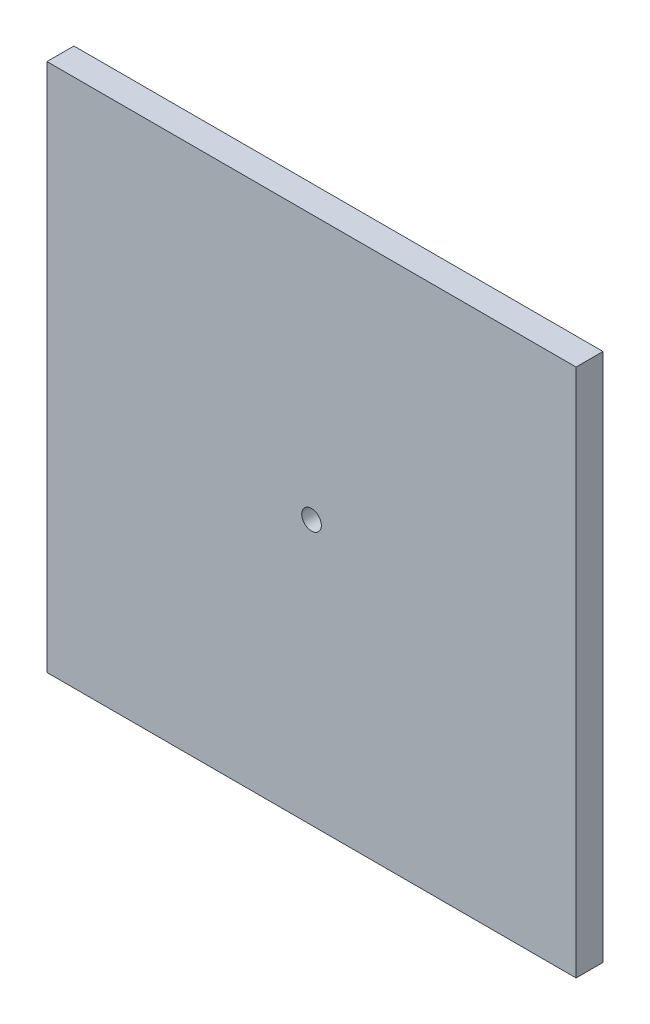
SolidWorks part; units mm, degrees
ref_plane "Front Plane" through (0, 0, 0) normal (0, 0, 1) x (1, 0, 0)
ref_plane "Top Plane" through (0, 0, 0) normal (0, 1, 0) x (1, 0, 0)
ref_plane "Right Plane" through (0, 0, 0) normal (1, 0, 0) x (0, 0, -1)
sketch "Sketch1" plane through (0, 0, 0) normal (0, 0, 1) x (1, 0, 0)
  line L0 (0, 0) -> (-21.7183, -59.6705) construction
  line L1 (-85.725, 85.725) -> (85.725, 85.725)
  line L2 (-85.725, 85.725) -> (-85.725, -85.725)
  line L3 (-85.725, -85.725) -> (85.725, -85.725)
  line L4 (85.725, 85.725) -> (85.725, -85.725)
  line L5 (0, 0) -> (0, -76.9938) construction
  line L6 (-27.4443, 76.9938) -> (31.5245, 76.9938) construction
  circle A0 centre (0, 0) radius 76.9938
  circle A1 centre (-21.7183, -59.6705) radius 3.175
  circle A2 centre (0, 0) radius 3.175
  circle A3 centre (-40.817, 48.6438) radius 3.175
  circle A4 centre (62.5353, 11.0267) radius 3.175
  circle A5 centre (-73.025, 73.025) radius 3.175
  circle A6 centre (73.025, 73.025) radius 3.175
  circle A7 centre (73.025, -73.025) radius 3.175
  circle A8 centre (-73.025, -73.025) radius 3.175
  point P12 (0, 85.725)
  point P18 (0, 0)
  point P23 (-85.725, 0)
  point P29 (0, 0)
  dimension "D1" = 153.9875
  dimension "D4" = 6.35
  dimension "D5" = 6.35
  dimension "D7" = 6.35
  dimension "D2" = 63.5
  dimension "D3" = 20
  dimension "D8" = 12.7
  dimension "D9" = 90
  dimension "D10" = 12.7
  dimension "D11" = 4
  dimension "D12" = 85.725
  dimension "D13" = 8.7312
  dimension "D6" = 3
extrude "Boss-Extrude1" add sketch "Sketch1" along normal blind 8.7312 contours L4 L1 L2 L3 A8 A7 A6 A5 A0 | A6 | A5 | A8 | A7 | A1 | A3 | A4 | A0 A4 A3 A2 A1 region at (0, 83.3003, 0) region at (-74.816, 0, 0) region at (-21.7183, -59.6705, 0) region at (-40.817, 48.6438, 0) region at (62.5353, 11.0267, 0) region at (-73.025, 73.025, 0) region at (73.025, 73.025, 0) region at (73.025, -73.025, 0) region at (-73.025, -73.025, 0)
extrude "Boss-Extrude4" add sketch "Sketch1<5>" against normal blind 9.398 contours A6 | A5 | A8 | A7 region at (-73.025, 73.025, 0) region at (73.025, 73.025, 0) region at (73.025, -73.025, 0) region at (-73.025, -73.025, 0)
sketch "Sketch1<5>" plane through (0, 0, 0) normal (0, 0, 1) x (1, 0, 0) same geometry as "Sketch1"
